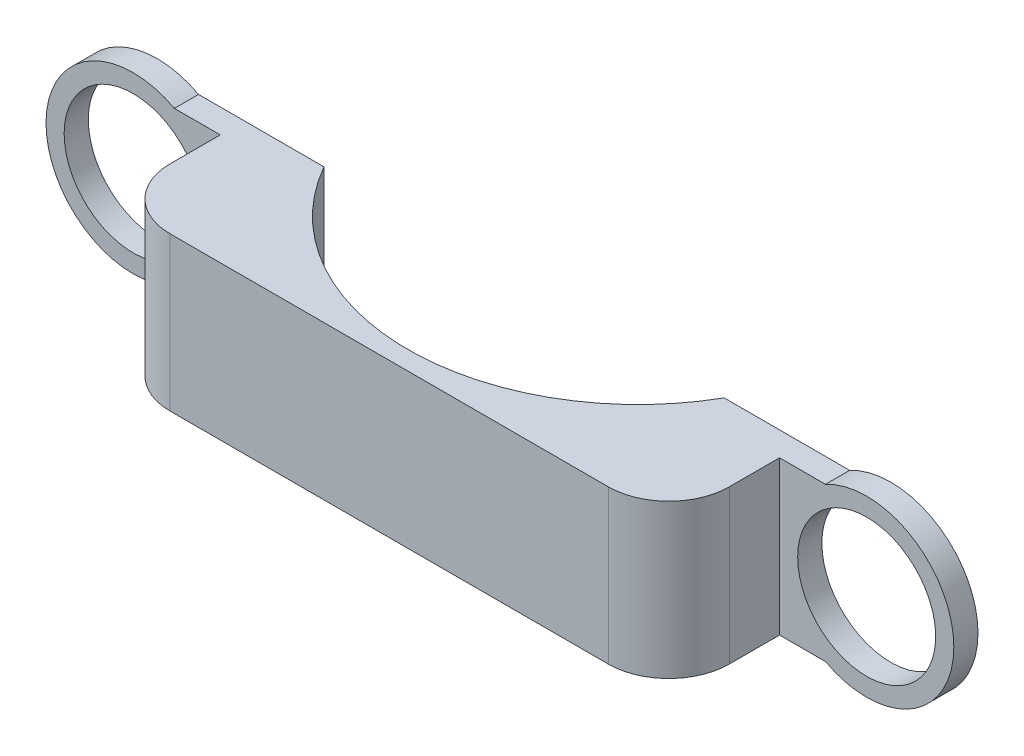
SolidWorks part; units mm, degrees
ref_plane "Front Plane" through (0, 0, 0) normal (0, 0, 1) x (1, 0, 0)
ref_plane "Top Plane" through (0, 0, 0) normal (0, 1, 0) x (1, 0, 0)
ref_plane "Right Plane" through (0, 0, 0) normal (1, 0, 0) x (0, 0, -1)
sketch "Sketch1" plane through (0, 0, 0) normal (0, 1, 0) x (1, 0, 0)
  line L0 (30.4746, -22.8672) -> (46.26, -22.8672)
  line L1 (-46.26, -22.8672) -> (-30.4746, -22.8672)
  line L2 (-46.26, -22.8672) -> (-46.26, -41.1872)
  line L3 (-46.26, -41.1872) -> (46.26, -41.1872)
  line L4 (46.26, -22.8672) -> (46.26, -41.1872)
  arc A0 (-30.4746, -22.8672) -> (30.4746, -22.8672) centre (0, 0) ccw
  dimension "D1" = 76.2
  dimension "D2" = 18.32
  dimension "D3" = 92.52
  dimension "D4" = 46.26
extrude "Boss-Extrude1" add sketch "Sketch1" along normal blind 25.4
sketch "Sketch2" plane through (0, 0, 22.8672) normal (0, 0, -1) x (-1, 0, 0)
  line L0 (-46.26, 0) -> (-30.4746, 0) construction
  line L1 (-46.26, 25.4) -> (-30.4746, 25.4)
  line L2 (-46.26, 25.4) -> (-46.26, 0)
  line L3 (-46.26, 0) -> (-30.4746, 0)
  line L4 (-30.4746, 25.4) -> (-30.4746, 0)
  line L5 (30.4746, 0) -> (46.26, 0) construction
  line L6 (46.26, 25.4) -> (30.4746, 25.4)
  line L7 (46.26, 25.4) -> (46.26, 0)
  line L8 (46.26, 0) -> (30.4746, 0)
  line L9 (30.4746, 25.4) -> (30.4746, 0)
extrude "Boss-Extrude2" add sketch "Sketch2" along normal blind 4
sketch "Sketch3" plane through (0, 0, 18.8672) normal (0, 0, -1) x (-1, 0, 0)
  line L0 (-46.26, 25.4) -> (-46.26, 0) construction
  line L1 (46.26, 0) -> (46.26, 25.4) construction
  line L2 (46.26, 25.4) -> (30.4746, 25.4) construction
  circle A0 centre (-60.675, 12.7) radius 11.415
  circle A1 centre (-60.675, 12.7) radius 14.415
  circle A2 centre (60.675, 12.7) radius 14.415
  circle A3 centre (60.675, 12.7) radius 11.415
  dimension "D1" = 22.83
  dimension "D2" = 28.83
  dimension "D4" = 28.83
  dimension "D5" = 3
  dimension "D3" = 14.415
  dimension "D6" = 14.415
  dimension "D7" = 12.7
  dimension "D8" = 12.7
extrude "Boss-Extrude4" add sketch "Sketch3" against normal blind 4 separate body
sketch "Sketch4" plane through (0, 0, 18.8672) normal (0, 0, -1) x (-1, 0, 0)
  line L1 (-38.7003, 0) -> (-38.7003, 25.4)
  line L2 (-30.4746, 25.4) -> (-46.26, 25.4) construction
  line L3 (-38.7003, 25.4) -> (-56.6591, 25.4)
  line L4 (-56.6591, 25.4) -> (-49.26, 18.9125)
  line L5 (-38.7003, 0) -> (-49.3577, 0)
  line L6 (-46.26, 0) -> (-30.4746, 0) construction
  line L7 (-49.3577, 0) -> (-57.7546, 0)
  line L8 (-57.7546, 0) -> (-48.4801, 6.8687)
  line L9 (-48.4801, 6.8687) -> (-49.26, 18.9125)
  line L10 (46.26, 25.4) -> (46.26, 0)
  line L11 (46.26, 0) -> (46.26, 25.4) construction
  line L12 (46.26, 0) -> (56.6591, 0)
  line L13 (56.6591, 0) -> (49.09, 6.8687)
  line L14 (49.09, 6.8687) -> (48.3277, 16.397)
  line L15 (48.3277, 16.397) -> (56.2568, 25.4)
  line L16 (56.2568, 25.4) -> (46.26, 25.4)
  point P21 (-49.26, 18.9125)
  point P22 (-48.0228, 8.5456)
  point P23 (-48.4801, 6.8687)
  point P24 (48.3277, 16.397)
  point P25 (49.09, 6.8687)
extrude "Boss-Extrude5" add sketch "Sketch4" against normal blind 4
fillet "Fillet1" radius 10 2 edges at (46.26, 12.7, 41.1872) (-46.26, 12.7, 41.1872)
sketch "Sketch5" plane through (0, 0, 0) normal (0, 1, 0) x (1, 0, 0)
  circle A0 centre (0, 0) radius 38.1
extrude "Cut-Extrude1" cut sketch "Sketch5" along normal up to surface (25.4 mm away) up to face at (0, 25.4, 26.9139)
